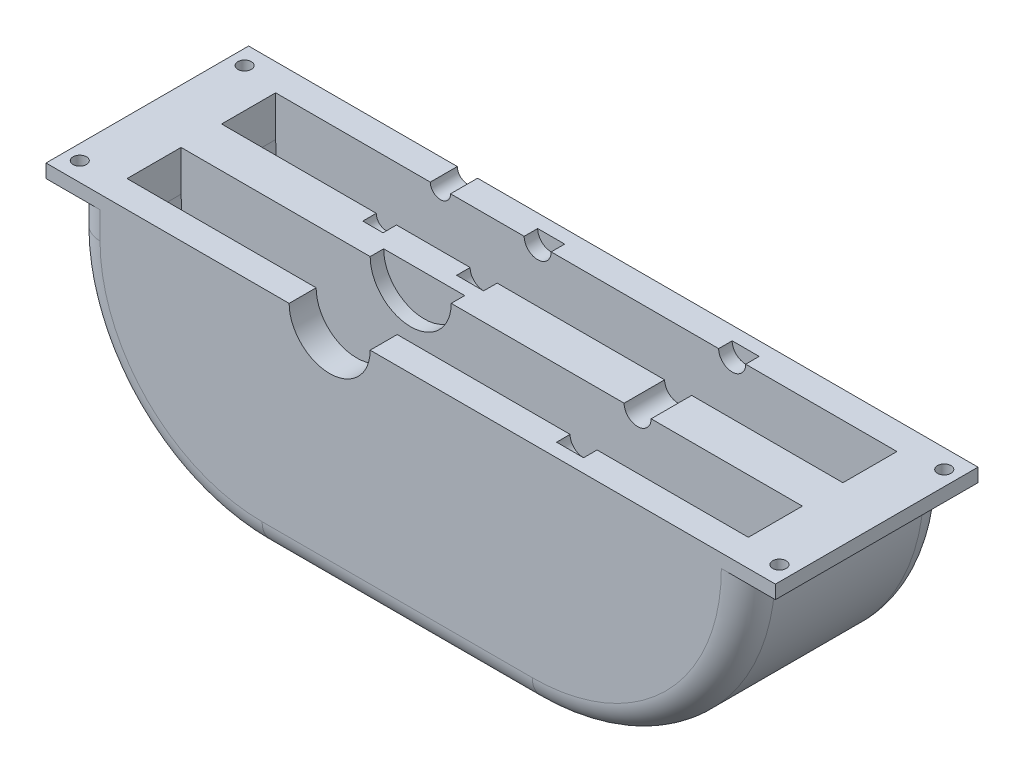
SolidWorks part; units mm, degrees
ref_plane "Front Plane" through (0, 0, 0) normal (0, 0, 1) x (1, 0, 0)
ref_plane "Top Plane" through (0, 0, 0) normal (0, 1, 0) x (1, 0, 0)
ref_plane "Right Plane" through (0, 0, 0) normal (1, 0, 0) x (0, 0, -1)
sketch "Sketch1" plane through (0, 0, 0) normal (0, 0, 1) x (1, 0, 0)
  line L1 (125, 0) -> (-125, 0)
  line L2 (125, 0) -> (125, -5)
  line L3 (45, -85) -> (-55, -85)
  line L4 (-125, 0) -> (-125, -15)
  arc A0 (125, -5) -> (45, -85) centre (45, -5) cw
  arc A1 (-55, -85) -> (-125, -15) centre (-55, -15) cw
  dimension "D2" = 80
  dimension "D3" = 70
  dimension "D1" = 250
  dimension "D4" = 85
extrude "Boss-Extrude1" add sketch "Sketch1" along normal mid plane 75 contours L1 L4 A1 L3 A0 L2
shell "Shell1" thickness 10 removed face at (0, 0, 0)
sketch "Sketch2" plane through (0, 0, 0) normal (0, 1, 0) x (1, 0, 0)
  line L0 (-115, -27.5) -> (-115, 27.5) construction
  line L1 (-115, 7.5) -> (115, 7.5)
  line L2 (-115, 7.5) -> (-115, -7.5)
  line L3 (-115, -7.5) -> (115, -7.5)
  line L4 (115, 7.5) -> (115, -7.5)
  line L5 (115, -27.5) -> (115, 27.5) construction
  line L6 (-115, 7.5) -> (115, -7.5) construction
  dimension "D1" = 15
extrude "Boss-Extrude3" add sketch "Sketch2" against normal up to surface (75 mm away) contours L1 L4 L3 L2 up to face at (-5, -75, 0)
extrude "Cut-Extrude2" cut sketch "Sketch1<4>" against normal through all both and the other way through all flip side to cut
sketch "Sketch1<4>" plane through (0, 0, 0) normal (0, 0, 1) x (1, 0, 0) same geometry as "Sketch1"
sketch "Sketch3" plane through (0, 0, -37.5) normal (0, 0, -1) x (-1, 0, 0)
  line L0 (-125, 0) -> (125, 0) construction
  circle A0 centre (30, 0) radius 15
  circle A1 centre (30, 0) radius 72
  circle A2 centre (-54, 0) radius 12
  circle A3 centre (-54, 0) radius 5
  circle A4 centre (-54, 0) radius 48
  circle A5 centre (18, 0) radius 24
  circle A6 centre (54, 0) radius 12
  circle A8 centre (54, 0) radius 3.75
  circle A9 centre (18, 0) radius 5
  point P5 (0, 0)
  point P17 (0, 0)
  point P18 (0, 0)
  line M2 (125, 0) -> (-125, 0)
  dimension "D1" = 30
  dimension "D3" = 144
  dimension "D4" = 24
  dimension "D5" = 10
  dimension "D6" = 96
  dimension "D7" = 48
  dimension "D8" = 24
  dimension "D10" = 10
  dimension "7.5" = 7.5
  dimension "D2" = 85
sketch "Sketch4" plane through (0, 0, 0) normal (0, 1, 0) x (1, 0, 0)
  line L0 (0, 37.5) -> (0, -37.5) construction
  line L1 (125, 37.5) -> (-125, 37.5) construction
  line L2 (125, -37.5) -> (-125, -37.5) construction
  line L3 (-135, 37.5) -> (-135, -37.5)
  line L4 (125, 37.5) -> (135, 37.5)
  line L5 (125, 37.5) -> (125, -37.5)
  line L6 (125, -37.5) -> (135, -37.5)
  line L7 (135, 37.5) -> (135, -37.5)
  line L8 (-125, -37.5) -> (-135, -37.5)
  line L9 (-125, 37.5) -> (-125, -37.5)
  line L10 (-125, 37.5) -> (-135, 37.5)
  circle A0 centre (129.5, 30.5) radius 2.5
  circle A1 centre (129.5, -30.5) radius 2.5
  circle A2 centre (-129.5, -30.5) radius 2.5
  circle A3 centre (-129.5, 30.5) radius 2.5
  dimension "D2" = 5
  dimension "D1" = 10
  dimension "D3" = 7
  dimension "D4" = 5.5
  dimension "D5" = 7
extrude "Boss-Extrude4" add sketch "Sketch4" against normal blind 5
fillet "Fillet1" radius 10 8 edges at (-125, -10, 37.5) (-104.4975, -64.4975, 37.5) (-5, -85, 37.5) (-125, -10, -37.5) (-104.4975, -64.4975, -37.5) (-5, -85, -37.5) (101.5685, -61.5685, 37.5) (101.5685, -61.5685, -37.5)
extrude "Cut-Extrude3" cut sketch "Sketch3" against normal offset from surface (35 mm away) 10 contours A8 up to face at (-1.3215, -32.8206, 7.5)
extrude "Cut-Extrude4" cut sketch "Sketch3<13>" along direction (0, 0, 1) on the side of the normal offset from surface (35 mm away) 10 from surface contours A9 A0 M2 | A0 A9 M2 | A9 A5 A0 M2 | A9 A0 A5 M2 | A6 A0 M2 | A6 A5 A0 | A0 A6 M2 | A6 A0 A5 region at (-43.5343, 2.3203, -37.5) region at (-43.5343, -2.3203, -37.5) region at (-41.6597, 7.1083, -37.5) region at (-41.6597, -7.1083, -37.5) region at (-30.1159, 6.9675, -37.5) region at (-30.1159, -6.9675, -37.5) region at (-18.7215, 2.1926, -37.5) region at (-18.7215, -2.1926, -37.5) up to face at (-14.4911, -25.0842, -7.5) starting at face at (-13.6588, -23.5471, 37.5)
sketch "Sketch3<13>" plane through (0, 0, -37.5) normal (0, 0, -1) x (-1, 0, 0) same geometry as "Sketch3"
extrude "Cut-Extrude5" cut sketch "Sketch3<14>" along direction (0, 0, -1) on the side against the normal offset from surface (65 mm away) 5 from offset 5 contours A3 M2 | A3 M2 region at (54, 2.1221, -37.5) region at (54, -2.1221, -37.5) up to face at (-16.6299, -20.6294, 37.5) offset against normal yes
sketch "Sketch3<14>" plane through (0, 0, -37.5) normal (0, 0, -1) x (-1, 0, 0) same geometry as "Sketch3"
extrude "Cut-Extrude6" cut sketch "Sketch3<15>" against normal offset from surface (30 mm away) 10 from offset 5 contours A9 A0 M2 | A0 A9 M2 | A9 region at (-18.7215, 2.1926, -37.5) region at (-18.7215, -2.1926, -37.5) up to face at (4.0071, -21.6924, 7.5) offset against normal yes
sketch "Sketch3<15>" plane through (0, 0, -37.5) normal (0, 0, -1) x (-1, 0, 0) same geometry as "Sketch3"
